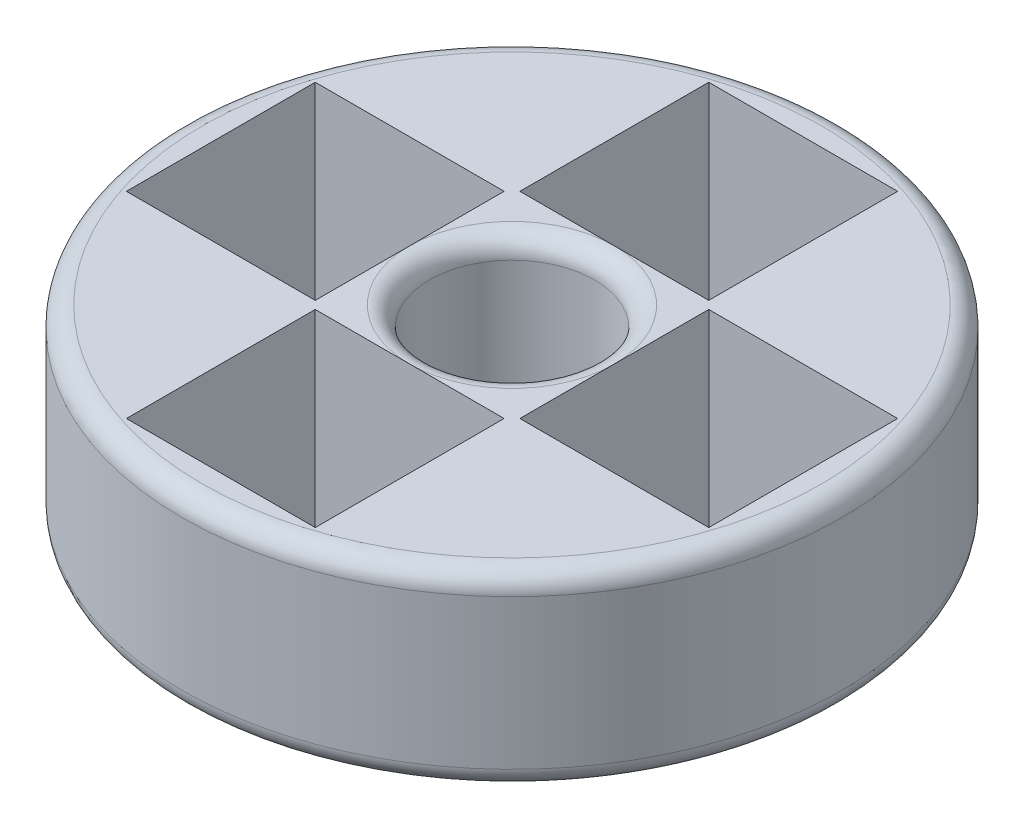
SolidWorks part; units mm, degrees
ref_plane "Ebene vorne" through (0, 0, 0) normal (0, 0, 1) x (1, 0, 0)
ref_plane "Ebene oben" through (0, 0, 0) normal (0, 1, 0) x (1, 0, 0)
ref_plane "Ebene rechts" through (0, 0, 0) normal (1, 0, 0) x (0, 0, -1)
sketch "Skizze1" plane through (0, 0, 0) normal (0, 1, 0) x (1, 0, 0)
  line L0 (0, -55) -> (0, 55) construction
  line L1 (-4.8, 5.2) -> (4.8, 5.2)
  line L2 (-4.8, 5.2) -> (-4.8, 14.8)
  line L3 (-4.8, 14.8) -> (4.8, 14.8)
  line L4 (4.8, 5.2) -> (4.8, 14.8)
  line L5 (-4.8, 5.2) -> (4.8, 14.8) construction
  line L6 (-4.8, 14.8) -> (4.8, 5.2) construction
  line L7 (5.2, 4.8) -> (14.8, 4.8)
  line L8 (5.2, 4.8) -> (5.2, -4.8)
  line L9 (5.2, -4.8) -> (14.8, -4.8)
  line L10 (14.8, 4.8) -> (14.8, -4.8)
  line L11 (4.8, -5.2) -> (4.8, -14.8)
  line L12 (4.8, -5.2) -> (-4.8, -5.2)
  line L13 (-4.8, -5.2) -> (-4.8, -14.8)
  line L14 (4.8, -14.8) -> (-4.8, -14.8)
  line L15 (-5.2, -4.8) -> (-14.8, -4.8)
  line L16 (-5.2, -4.8) -> (-5.2, 4.8)
  line L17 (-5.2, 4.8) -> (-14.8, 4.8)
  line L18 (-14.8, -4.8) -> (-14.8, 4.8)
  circle A1 centre (0, 0) radius 16.75
  circle A2 centre (0, 0) radius 4.2
  point P0 (0, 10)
  point P23 (0, 0)
  dimension "D5" = 33.5
  dimension "D6" = 8.4
  dimension "D1" = 9.6
  dimension "D2" = 9.6
  dimension "D3" = 10
  dimension "D4" = 4
extrude "Aufsatz-Linear austragen1" add sketch "Skizze1" along normal blind 9.6
fillet "Verrundung1" radius 1 4 edges at (0, 0, 4.2) (0, 9.6, 4.2) (0, 0, 16.75) (0, 9.6, 16.75)
